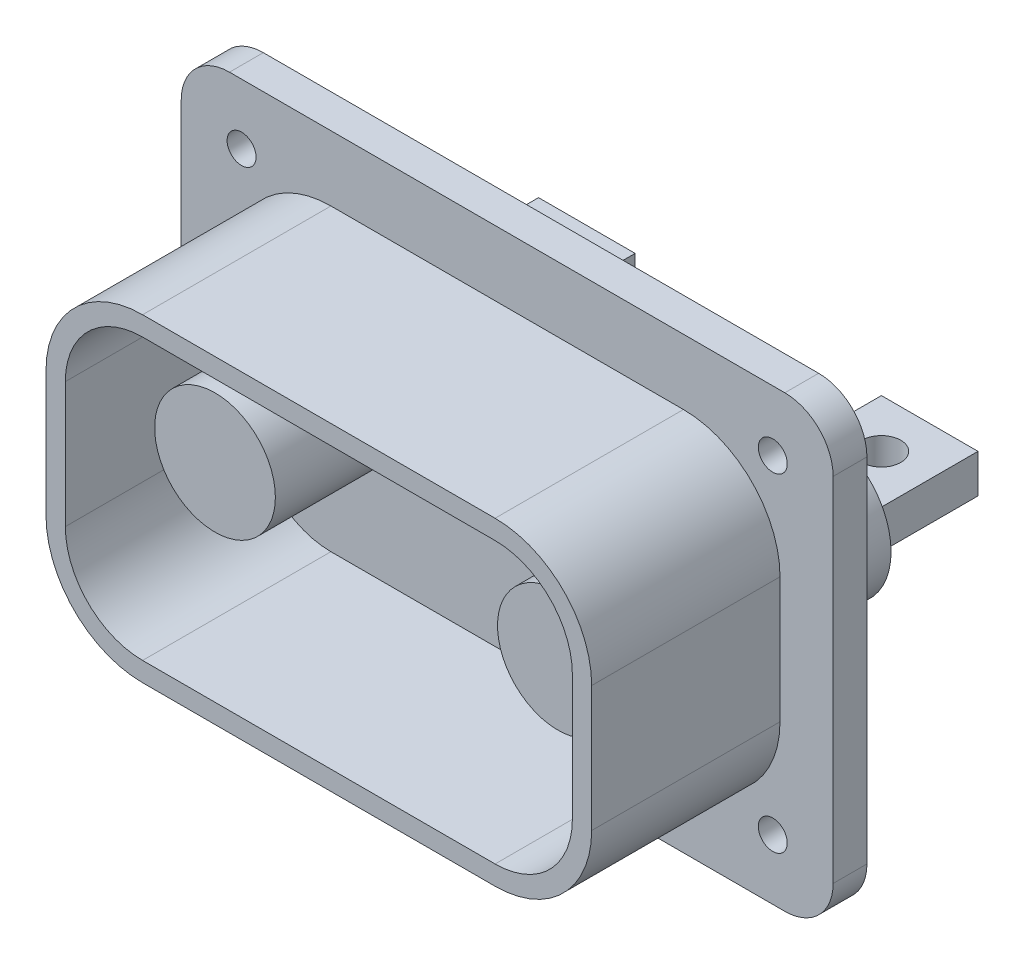
SolidWorks part; units mm, degrees
material "Custom Plastic"
ref_plane "X-Y Datum" through (0, 0, 0) normal (0, 0, 1) x (1, 0, 0)
ref_plane "X-Z Datum" through (0, 0, 0) normal (0, 1, 0) x (1, 0, 0)
ref_plane "Y-Z Datum" through (0, 0, 0) normal (1, 0, 0) x (0, 0, -1)
sketch "Sketch1" plane through (0, 0, 0) normal (0, 0, 1) x (1, 0, 0)
  line L1 (-67.5, -46.5) -> (67.5, -46.5)
  line L2 (-67.5, -46.5) -> (-67.5, 46.5)
  line L3 (-67.5, 46.5) -> (67.5, 46.5)
  line L4 (67.5, -46.5) -> (67.5, 46.5)
  line L5 (-67.5, -46.5) -> (67.5, 46.5) construction
  line L6 (-67.5, 46.5) -> (67.5, -46.5) construction
  line L11 (-50.4972, -34.787) -> (50.4972, 34.787) construction
  line L12 (-50.4972, 34.787) -> (50.4972, -34.787) construction
  line L13 (-55, 34) -> (55, 34) construction
  line L14 (-55, 34) -> (-55, -34) construction
  line L15 (-55, -34) -> (55, -34) construction
  line L16 (55, 34) -> (55, -34) construction
  line L17 (-55, 34) -> (55, -34) construction
  line L18 (-55, -34) -> (55, 34) construction
  circle A4 centre (-55, 34) radius 3
  circle A5 centre (55, 34) radius 3
  circle A6 centre (55, -34) radius 3
  circle A7 centre (-55, -34) radius 3
  point P0 (0, 0)
  point P6 (0, 0)
  point P12 (0, 0)
  dimension "D3" = 110
  dimension "D4" = 68
  dimension "D5" = 6
  dimension "D1" = 135
  dimension "D2" = 93
extrude "Boss-Extrude1" add sketch "Sketch1" along normal blind 7 contours L1 L4 L3 L2 A4 | A4 region at (0, 0, 0)
sketch "Sketch2" plane through (0, 0, 7) normal (0, 0, 1) x (1, 0, 0)
  line L0 (-35.5, 0) -> (35.5, 0) construction
  line L5 (-52.5, 13) -> (-52.5, -13)
  line L6 (-36.5, 33) -> (36.5, 33)
  line L7 (-56.5, 13) -> (-56.5, -13)
  line L8 (-36.5, -33) -> (36.5, -33)
  line L9 (56.5, 13) -> (56.5, -13)
  line L10 (-56.5, 33) -> (56.5, -33) construction
  line L11 (-56.5, -33) -> (56.5, 33) construction
  line L12 (-36.5, -29) -> (36.5, -29)
  line L13 (52.5, 13) -> (52.5, -13)
  line L14 (-36.5, 29) -> (36.5, 29)
  circle A4 centre (-35.5, 0) radius 4 construction
  circle A5 centre (35.5, 0) radius 4 construction
  arc A6 (36.5, -33) -> (56.5, -13) centre (36.5, -13) ccw
  arc A7 (36.5, 33) -> (56.5, 13) centre (36.5, 13) cw
  arc A8 (-36.5, 33) -> (-56.5, 13) centre (-36.5, 13) ccw
  arc A9 (-56.5, -13) -> (-36.5, -33) centre (-36.5, -13) ccw
  arc A10 (-52.5, -13) -> (-36.5, -29) centre (-36.5, -13) ccw
  arc A11 (36.5, -29) -> (52.5, -13) centre (36.5, -13) ccw
  arc A12 (36.5, 29) -> (52.5, 13) centre (36.5, 13) cw
  arc A13 (-36.5, 29) -> (-52.5, 13) centre (-36.5, 13) ccw
  point P2 (0, 0)
  point P4 (0, 0)
  dimension "D1" = 8
  dimension "D5" = 20
  dimension "D2" = 71
  dimension "D3" = 113
  dimension "D4" = 66
  dimension "D6" = 4
extrude "Boss-Extrude2" add sketch "Sketch2" along normal blind 39
fillet "Fillet1" radius 10 4 edges at (67.5, 46.5, 3.5) (67.5, -46.5, 3.5) (-67.5, -46.5, 3.5) (-67.5, 46.5, 3.5)
sketch "Sketch3" plane through (0, 0, 0) normal (0, 0, -1) x (-1, 0, 0)
  line L0 (-35.5, 0) -> (35.5, 0) construction
  circle A0 centre (-35.5, 0) radius 15
  circle A1 centre (35.5, 0) radius 15
  point P11 (0, 0)
  dimension "D1" = 71
  dimension "D2" = 30
extrude "Boss-Extrude3" add sketch "Sketch3" along normal blind 22 contours A0 | A1 region at (35.5, 0, 0) region at (-35.5, 0, 0)
sketch "Sketch5" plane through (0, 0, -22) normal (0, 0, -1) x (-1, 0, 0)
  line L1 (-45.5, 4) -> (-25.5, 4)
  line L2 (-45.5, 4) -> (-45.5, -4)
  line L3 (-45.5, -4) -> (-25.5, -4)
  line L4 (-25.5, 4) -> (-25.5, -4)
  line L5 (-45.5, 4) -> (-25.5, -4) construction
  line L6 (-45.5, -4) -> (-25.5, 4) construction
  line L7 (25.5, 4) -> (45.5, 4)
  line L8 (25.5, 4) -> (25.5, -4)
  line L9 (25.5, -4) -> (45.5, -4)
  line L10 (45.5, 4) -> (45.5, -4)
  line L11 (25.5, 4) -> (45.5, -4) construction
  line L12 (25.5, -4) -> (45.5, 4) construction
  point P0 (-35.5, 0)
  point P6 (35.5, 0)
  dimension "D1" = 8
  dimension "D2" = 20
extrude "Boss-Extrude4" add sketch "Sketch5" along normal blind 23
sketch "Sketch6" plane through (0, 4, 0) normal (0, 1, 0) x (1, 0, 0)
  line L0 (35.5, 45) -> (35.5, 22) construction
  line L1 (25.5, 45) -> (45.5, 45) construction
  line L2 (50.5, 22) -> (20.5, 22) construction
  line L3 (0, -43.0151) -> (0, 43.0151) construction
  circle A0 centre (35.5, 35) radius 4
  circle A1 centre (-35.5, 35) radius 4
  point P8 (35.5, 34.9994)
  dimension "D1" = 8
  dimension "D2" = 10
extrude "Cut-Extrude1" cut sketch "Sketch6" against normal through all
sketch "Sketch7" plane through (0, 0, 7) normal (0, 0, 1) x (1, 0, 0)
  line L0 (-35.5, 0) -> (35.5, 0) construction
  circle A0 centre (-35.5, 0) radius 12.5
  circle A1 centre (35.5, 0) radius 12.5
  point P4 (0, 0)
  dimension "D2" = 25
  dimension "D1" = 71
extrude "Boss-Extrude5" add sketch "Sketch7" along normal blind 25
